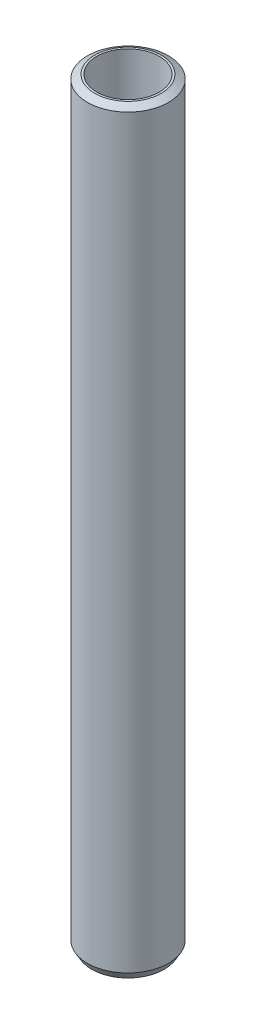
SolidWorks part; units mm, degrees
ref_plane "Front Plane" through (0, 0, 0) normal (0, 0, 1) x (1, 0, 0)
ref_plane "Top Plane" through (0, 0, 0) normal (0, 1, 0) x (1, 0, 0)
ref_plane "Right Plane" through (0, 0, 0) normal (1, 0, 0) x (0, 0, -1)
sketch "Sketch1" plane through (0, 0, 0) normal (0, 1, 0) x (1, 0, 0)
  circle A0 centre (0, 0) radius 17.5
  dimension "SHAFT_OD" = 35
extrude "Boss-Extrude1" add sketch "Sketch1" along normal blind 327.0975
sketch "Sketch2" plane through (0, 0, 0) normal (0, 1, 0) x (1, 0, 0)
  circle A0 centre (0, 0) radius 13.4672
  dimension "BORE_D" = 26.9344
extrude "Cut-Extrude1" cut sketch "Sketch2" along normal through all
chamfer "Chamfer1" distance 1.8136 angle 60 2 edges at (0, 327.0975, 17.5) (0, 0, 17.5) first distance on face at (0, 327.0975, 17.5) first distance on face at (0, 0, 13.4672)
